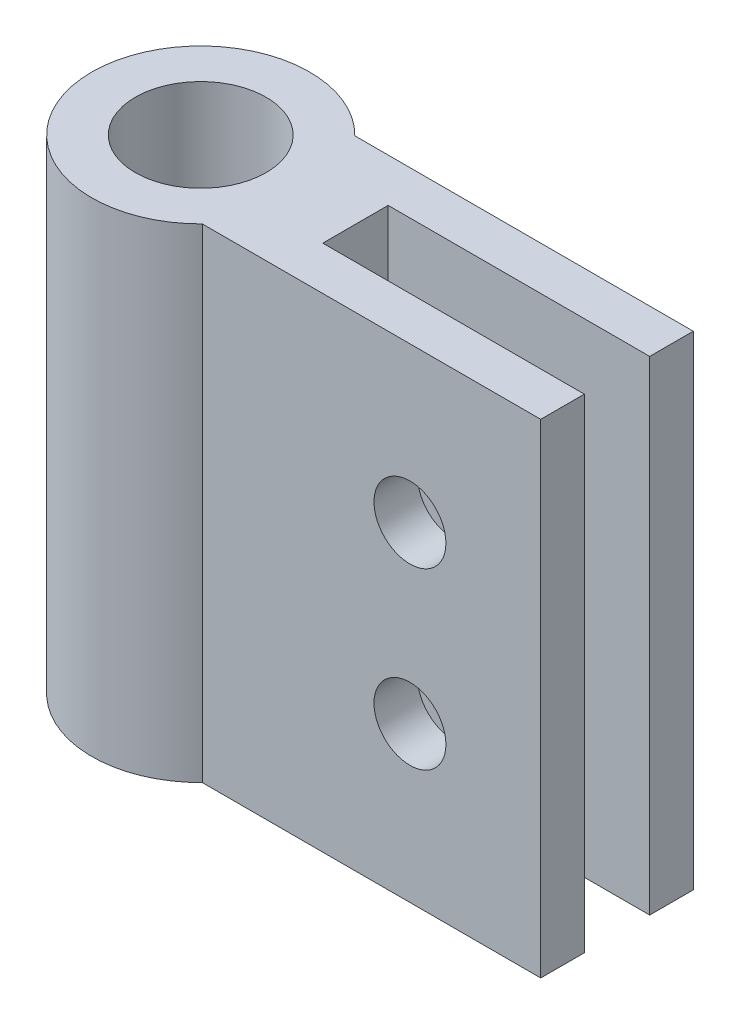
SolidWorks part; units mm, degrees
ref_plane "前视基准面" through (0, 0, 0) normal (0, 0, 1) x (1, 0, 0)
ref_plane "上视基准面" through (0, 0, 0) normal (0, 1, 0) x (1, 0, 0)
ref_plane "右视基准面" through (0, 0, 0) normal (1, 0, 0) x (0, 0, -1)
sketch "草图1" plane through (0, 0, 0) normal (0, 1, 0) x (1, 0, 0)
  circle A0 centre (0, 0) radius 3
  circle A1 centre (0, 0) radius 5
  dimension "D1" = 6
  dimension "D2" = 2
extrude "凸台-拉伸1" add sketch "草图1" along normal blind 22.2
sketch "草图2" plane through (0, 22.2, 0) normal (0, 1, 0) x (1, 0, 0)
  line L1 (19.1, -3.5) -> (3.1, -3.5)
  line L2 (19.1, -3.5) -> (19.1, 3.5)
  line L3 (19.1, 3.5) -> (3.1, 3.5)
  line L4 (3.1, -3.5) -> (3.1, 3.5)
  line L5 (19.1, -3.5) -> (3.1, 3.5) construction
  line L6 (19.1, 3.5) -> (3.1, -3.5) construction
  point P0 (11.1, 0)
  dimension "D1" = 11.1
  dimension "D2" = 16
  dimension "D3" = 7
extrude "凸台-拉伸2" add sketch "草图2" against normal up to surface (22.2 mm away) up to face at (0, 0, 5)
sketch "草图3" plane through (0, 22.2, 0) normal (0, 1, 0) x (1, 0, 0)
  line L0 (19.1, -3.5) -> (19.1, 3.5) construction
  line L1 (7.1, -1.5) -> (19.1, -1.5)
  line L2 (7.1, -1.5) -> (7.1, 1.5)
  line L3 (7.1, 1.5) -> (19.1, 1.5)
  line L4 (19.1, -1.5) -> (19.1, 1.5)
  line L5 (7.1, -1.5) -> (19.1, 1.5) construction
  line L6 (7.1, 1.5) -> (19.1, -1.5) construction
  point P0 (13.1, 0)
  dimension "D1" = 3
  dimension "D2" = 12
extrude "切除-拉伸1" cut sketch "草图3" against normal through all
sketch "草图4" plane through (0, 0, 3.5) normal (0, 0, 1) x (1, 0, 0)
  line L0 (7.1, 0) -> (7.1, 22.2) construction
  line L1 (7.1, 0) -> (7.1, 22.2) construction
  line L3 (19.1, 11.1) -> (3.5707, 11.1) construction
  line L4 (19.1, 0) -> (19.1, 22.2) construction
  line L5 (3.5707, 0) -> (3.5707, 22.2) construction
  circle A0 centre (13.1, 15.1) radius 1.65
  circle A2 centre (13.1, 7.1) radius 1.65
  dimension "D1" = 8
  dimension "D2" = 3.3
  dimension "D4" = 6
extrude "切除-拉伸2" cut sketch "草图4" against normal blind 22
